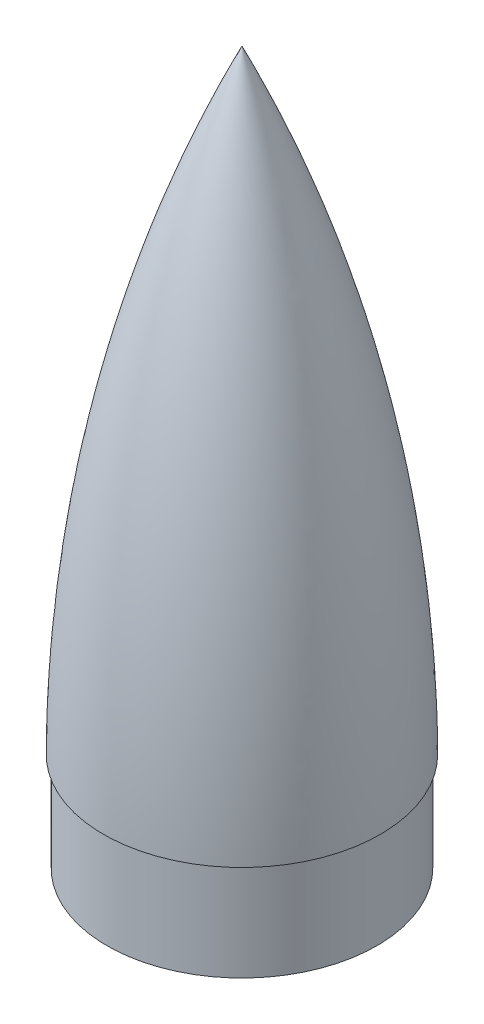
SolidWorks part; units mm, degrees
ref_plane "Front Plane" through (0, 0, 0) normal (0, 0, 1) x (1, 0, 0)
ref_plane "Top Plane" through (0, 0, 0) normal (0, 1, 0) x (1, 0, 0)
ref_plane "Right Plane" through (0, 0, 0) normal (1, 0, 0) x (0, 0, -1)
sketch "Croquis1" plane through (0, 0, 0) normal (1, 0, 0) x (0, 0, -1)
  line L0 (0, 0) -> (0, 290) construction
  line L1 (52, 10) -> (52, 77.802)
  line L3 (55, 40) -> (55, 0)
  line L4 (55, 0) -> (52, 0)
  line L5 (55, 40) -> (56.4, 40)
  line L6 (0, 290) -> (0, 282.8541)
  line L7 (52, 0) -> (0, 0)
  line L8 (0, 0) -> (0, 10)
  line L9 (0, 10) -> (52, 10)
  arc A0 (56.4, 40) -> (0, 290) centre (-539.2742, 36.9778) ccw
  arc A1 (52, 77.802) -> (0, 282.8541) centre (-539.2742, 36.9778) ccw
  arc A2 (53.4, 39.9848) -> (-2.7159, 288.7257) centre (-539.2742, 36.9778) ccw construction
  point P4 (0, 0)
  dimension "D7" = 595.6818
  dimension "D1" = 110
  dimension "D2" = 1.4
  dimension "D3" = 3
  dimension "D4" = 250
  dimension "D5" = 40
  dimension "D8" = 10
  dimension "D6" = 3
revolve "Revolución1" add sketch "Croquis1" angle 360 about L0
equation "\"R\" = ( \"L\" ^ 2 + \"Rn\" ^ 2 ) / ( 2 * \"Rn\" )'2"
equation "\"D7@Croquis1\"=\"R\""
equation "\"L\"=250"
equation "\"D4@Croquis1\"=\"L\""
equation "\"Diameter\"=110"
equation "\"D1@Croquis1\"=\"Diameter\""
equation "\"Rn\"= \"Diameter\" / 2"
